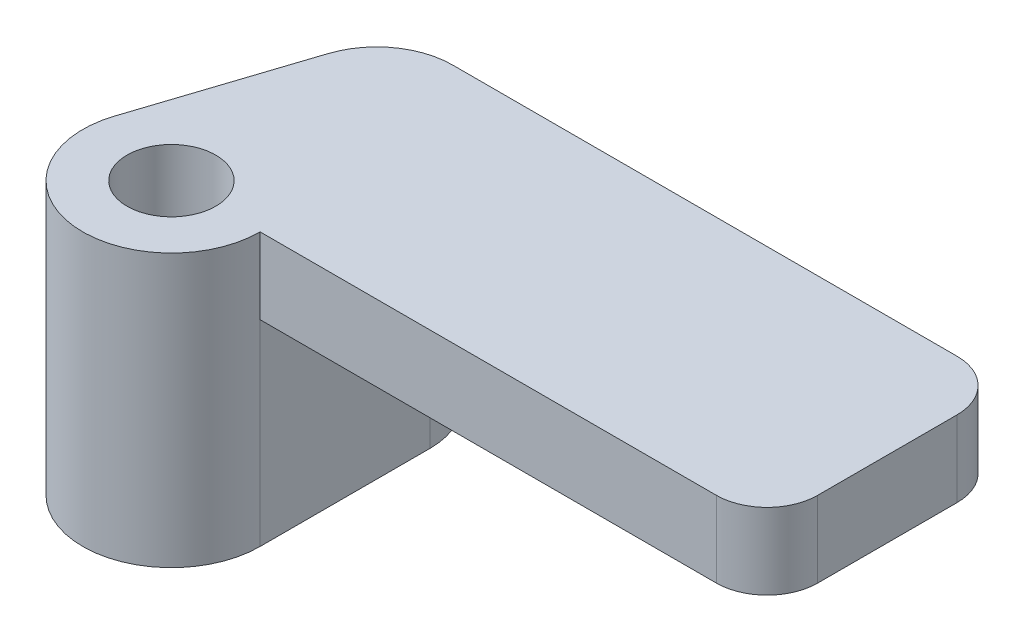
SolidWorks part; units mm, degrees
ref_plane "Front Plane" through (0, 0, 0) normal (0, 0, 1) x (1, 0, 0)
ref_plane "Top Plane" through (0, 0, 0) normal (0, 1, 0) x (1, 0, 0)
ref_plane "Right Plane" through (0, 0, 0) normal (1, 0, 0) x (0, 0, -1)
sketch "Sketch1" plane through (0, 0, 0) normal (0, 1, 0) x (1, 0, 0)
  line L1 (-10, -4.75) -> (10, -4.75)
  line L2 (-10, -4.75) -> (-10, 4.75)
  line L3 (-10, 4.75) -> (10, 4.75)
  line L4 (10, -4.75) -> (10, 4.75)
  line L5 (-10, -4.75) -> (10, 4.75) construction
  line L6 (-10, 4.75) -> (10, -4.75) construction
  point P0 (0, 0)
  dimension "D1" = 9.5
  dimension "D2" = 20
extrude "Boss-Extrude1" add sketch "Sketch1" along normal blind 3
sketch "Sketch2" plane through (0, 3, 0) normal (0, 1, 0) x (1, 0, 0)
  line L0 (-10, -4.75) -> (10, -4.75) construction
  line L1 (-13.5, -4.75) -> (-10, -4.75) construction
  line L2 (-10, 4.75) -> (-10, -4.75) construction
  line L3 (-14.0756, 4.75) -> (-16.8266, -3.6621)
  line L4 (-10, 4.75) -> (-14.0756, 4.75)
  line L5 (-10, 4.75) -> (-10, -4.75)
  circle A0 centre (-13.5, -4.75) radius 1.75
  circle A1 centre (-13.5, -4.75) radius 3.5 construction
  arc A2 (-16.8266, -3.6621) -> (-10, -4.75) centre (-13.5, -4.75) ccw
  point P11 (-14.0756, 4.75)
  dimension "D2" = 3.5
  dimension "D1" = 3.5
extrude "Boss-Extrude2" add sketch "Sketch2" against normal blind 10.75
fillet "Fillet1" radius 3 1 edges at (-14.0756, -2.375, -4.75)
fillet "Fillet2" radius 3 1 edges at (-10, -3.875, -4.75)
fillet "Fillet3" radius 2 2 edges at (10, 1.5, -4.75) (10, 1.5, 4.75)
